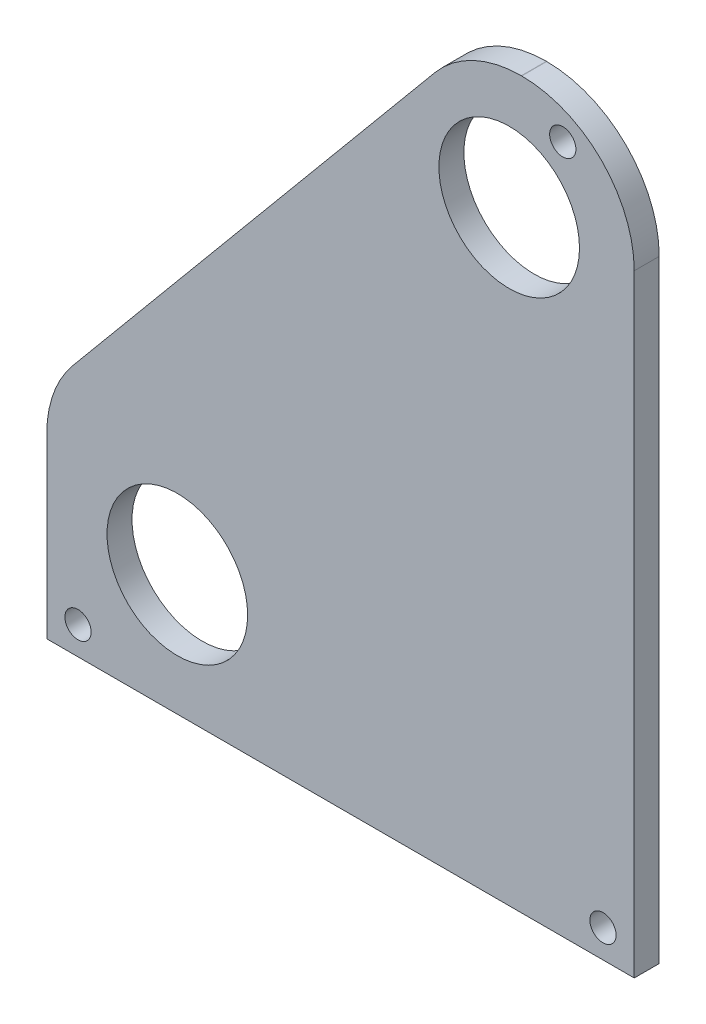
SolidWorks part; units mm, degrees
ref_plane "Front Plane" through (0, 0, 0) normal (0, 0, 1) x (1, 0, 0)
ref_plane "Top Plane" through (0, 0, 0) normal (0, 1, 0) x (1, 0, 0)
ref_plane "Right Plane" through (0, 0, 0) normal (1, 0, 0) x (0, 0, -1)
sketch "Sketch1" plane through (0, 0, 0) normal (0, 0, 1) x (1, 0, 0)
  line L0 (-88.6756, -72.1748) -> (-15.1004, 16.1745)
  line L1 (2.466, 24.4056) -> (2.5508, 24.4056)
  line L2 (-93.9692, -86.8036) -> (-93.9692, -122.9144)
  line L3 (-93.9692, -122.9144) -> (25.4108, -122.9144)
  line L4 (25.4108, 1.5456) -> (25.4108, -122.9144)
  line L5 (-51.6926, -27.7655) -> (25.4108, -122.9144) construction
  line L6 (-93.9692, -122.9144) -> (19.403, 16.9918) construction
  line L7 (-93.9692, -117.2353) -> (-87.6192, -117.2353) construction
  line L8 (-87.6192, -117.2353) -> (-87.6192, -123.5853) construction
  line L9 (25.4108, -117.2353) -> (19.0608, -117.2353) construction
  circle A0 centre (0, 0) radius 14.2875
  circle A1 centre (-67.4391, -98.331) radius 14.2875
  arc A4 (-88.6756, -72.1748) -> (-93.9692, -86.8036) centre (-71.1092, -86.8036) ccw
  arc A5 (-15.1004, 16.1745) -> (2.466, 24.4056) centre (2.466, 1.5456) cw
  arc A6 (2.5508, 24.4056) -> (25.4108, 1.5456) centre (2.5508, 1.5456) cw
  circle A7 centre (10.891, 16.9918) radius 2.667
  circle A8 centre (-87.6192, -117.2353) radius 2.667
  circle A9 centre (19.0608, -117.2353) radius 2.667
  point P5 (-34.2792, -49.2544)
  dimension "D1" = 22.86
  dimension "D2" = 6.35
extrude "Boss-Extrude1" add sketch "Sketch1" along normal blind 5.08
